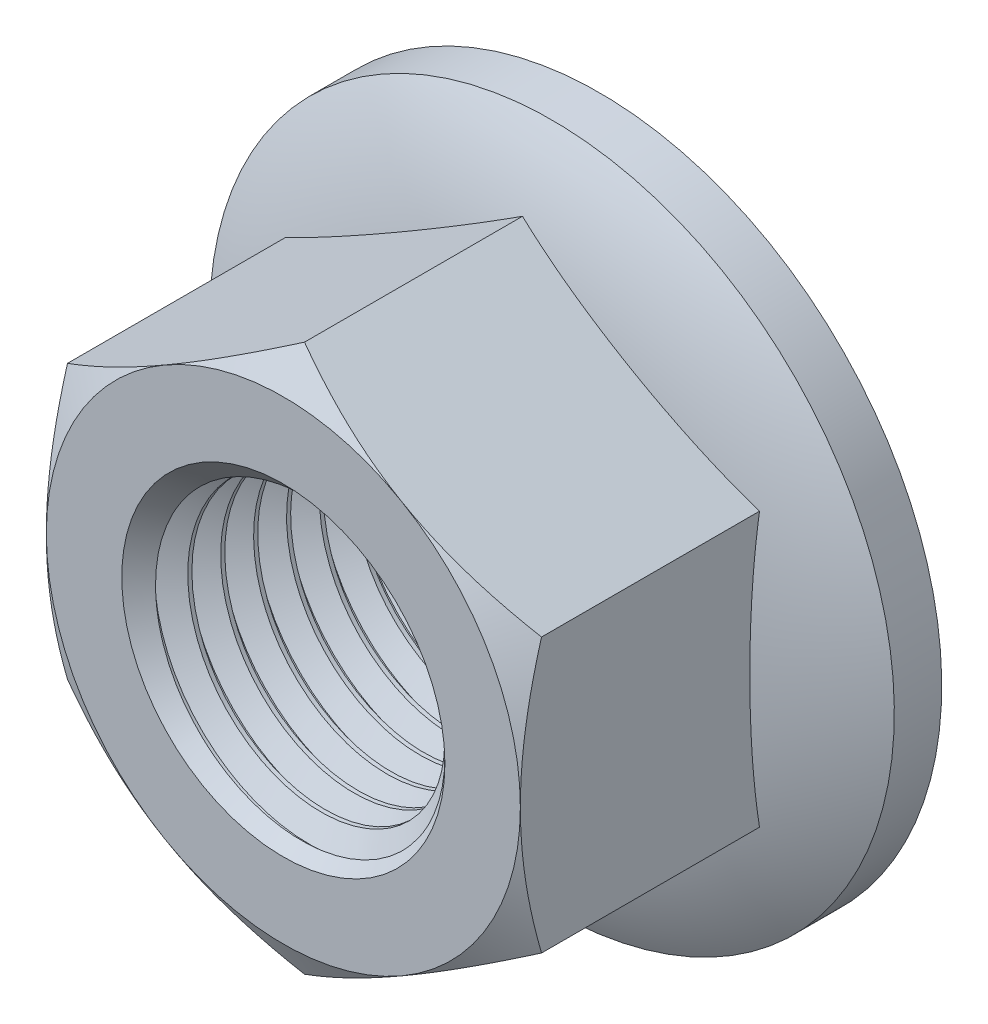
SolidWorks part; units mm, degrees
ref_plane "Front Plane" through (0, 0, 0) normal (0, 0, 1) x (1, 0, 0)
ref_plane "Top Plane" through (0, 0, 0) normal (0, 1, 0) x (1, 0, 0)
ref_plane "Right Plane" through (0, 0, 0) normal (1, 0, 0) x (0, 0, -1)
sketch "Sketch1" plane through (0, 0, 0) normal (0, 0, 1) x (1, 0, 0)
  line L1 (0, 10.3923) -> (-9, 5.1962)
  line L2 (-9, 5.1962) -> (-9, -5.1962)
  line L3 (-9, -5.1962) -> (0, -10.3923)
  line L4 (0, -10.3923) -> (9, -5.1962)
  line L5 (9, -5.1962) -> (9, 5.1962)
  line L6 (9, 5.1962) -> (0, 10.3923)
  circle A0 centre (0, 0) radius 9 construction
  dimension "Width" = 18
sketch "Sketch2" plane through (0, 0, 0) normal (1, 0, 0) x (0, 0, -1)
  line L0 (-6, 0) -> (6, 0) construction
  line L1 (6, 0) -> (6, 13)
  line L2 (6, 13) -> (4.2, 13)
  line L3 (4.2, 13) -> (4.2, 0)
  line L4 (-6, 0) -> (-6, 6)
  line L5 (-6, 6) -> (6, 6)
  line L6 (2.4, 6) -> (2.4, 13) construction
  line L7 (2.4, 13) -> (4.2, 13) construction
  arc A0 (4.2, 13) -> (2.4, 6) centre (16.9111, 6) ccw
  point P2 (0, 0)
  point P5 (-4.75, 6)
  point P12 (-6, -6)
  point P14 (-6, 6)
  dimension "Height" = 12
  dimension "Flange Diameter" = 26
  dimension "Flange Thickness" = 1.8
  dimension "Thread Diameter" = 12
  dimension "Thread Pitch" = 1.25
sketch "Sketch3" plane through (0, 0, 0) normal (0, 0, 1) x (1, 0, 0)
  line L0 (9, 5.1962) -> (0, 10.3923) construction
  line L1 (9, -5.1962) -> (9, 5.1962) construction
  line L2 (0, -10.3923) -> (9, -5.1962) construction
  line L3 (-9, -5.1962) -> (0, -10.3923) construction
  line L4 (-9, 5.1962) -> (-9, -5.1962) construction
  line L5 (0, 10.3923) -> (-9, 5.1962) construction
  line L6 (9, 5.1962) -> (0, 10.3923)
  line L7 (9, -5.1962) -> (9, 5.1962)
  line L8 (0, -10.3923) -> (9, -5.1962)
  line L9 (-9, -5.1962) -> (0, -10.3923)
  line L10 (-9, 5.1962) -> (-9, -5.1962)
  line L11 (0, 10.3923) -> (-9, 5.1962)
extrude "Boss-Extrude1" add sketch "Sketch3" against normal up to vertex (6 mm away) from vertex up to point (0, 0, -6) starting at point (0, 0, 6)
sketch "Sketch5" plane through (0, 0, 6) normal (0, 0, 1) x (1, 0, 0)
  circle A0 centre (0, 0) radius 9 construction
  circle A1 centre (0, 0) radius 9
extrude "Cut-Extrude1" cut sketch "Sketch5" against normal through all draft 60 flip side to cut
sketch "Sketch4" plane through (0, 0, 0) normal (1, 0, 0) x (0, 0, -1)
  line L0 (6, 13) -> (4.2, 13) construction
  line L1 (6, 13) -> (4.2, 13)
  line L2 (2.4, 6) -> (2.4, 0)
  line L3 (-6, 0) -> (6, 0) construction
  line L4 (2.4, 0) -> (6, 0)
  line L5 (6, 0) -> (6, 13)
  arc A0 (4.2, 13) -> (2.4, 6) centre (16.9111, 6) ccw construction
  arc A1 (4.2, 13) -> (2.4, 6) centre (16.9111, 6) ccw
revolve "Revolve1" add sketch "Sketch4" angle 360 about L4
sketch "Sketch6" plane through (0, 0, 6) normal (0, 0, 1) x (1, 0, 0)
  circle A0 centre (0, 0) radius 6
extrude "Cut-Extrude2" cut sketch "Sketch6" against normal through all
sketch "Sketch7" plane through (0, 0, 6) normal (0, 0, 1) x (1, 0, 0)
  circle A0 centre (0, 0) radius 6 construction
  circle A1 centre (0, 0) radius 6
ref_axis "Center Axis 1" through (0, 0, -6) along (0, 0, 1)
ref_plane "Contact Plane 1" through (0, 0, -6) normal (0, 0, -1) x (-1, 0, 0)
curve "Helix/Spiral1" pitch 1.25 height 13.25 radius 6 centre (0, 0, 6) axis (0, 0, -1) start towards (0, 1, 0)
sketch "Sketch8" plane through (0, 0, 0) normal (1, 0, 0) x (0, 0, -1)
  line L0 (-7.1719, 6.1353) -> (-6.5469, 5.0528) construction
  line L1 (-6.5469, 5.0528) -> (-5.9219, 6.1353) construction
  line L2 (-5.9219, 6.1353) -> (-7.1719, 6.1353) construction
  line L3 (-7.1328, 6.0677) -> (-5.9609, 6.0677)
  line L4 (-5.9609, 6.0677) -> (-6.4688, 5.1881)
  line L5 (-6.4688, 5.1881) -> (-6.625, 5.1881)
  line L6 (-6.625, 5.1881) -> (-7.1328, 6.0677)
  line L7 (-6.5469, 5.1881) -> (-6.5469, 5.0528) construction
  line L8 (-7.0938, 6) -> (-6, 6) construction
  line L9 (-6.5469, 6.1353) -> (-6.5469, 6) construction
  point P12 (-6.5469, 6.0677)
  dimension "D1" = 1.25
  dimension "D2" = 0.1562
sweep "Sweep1" add profiles "Sketch8" path "Helix/Spiral1"
sketch "Sketch9" plane through (0, 0, 6) normal (0, 0, 1) x (1, 0, 0)
  circle A0 centre (0, 0) radius 6.1353
extrude "Cut-Extrude3" cut sketch "Sketch9" against normal up to vertex (12 mm away) draft 45 and the other way through all up to point (0, 6, -6)
sketch "Sketch10" plane through (0, 0, -6) normal (0, 0, -1) x (-1, 0, 0)
  circle A1 centre (0, 0) radius 6.1353
  circle A2 centre (0, 0) radius 6.1353
  dimension "D1" = 0
extrude "Cut-Extrude4" cut sketch "Sketch10" against normal up to vertex (12 mm away) draft 45 and the other way through all up to point (0, 6, 6)
equation "\"D4@Helix/Spiral1\"=\"Thread Pitch@Sketch2\""
equation "\"D3@Helix/Spiral1\"=\"Height@Sketch2\"+\"Thread Pitch@Sketch2\""
equation "\"D2@Sketch8\"=\"D1@Sketch8\"/8"
equation "\"D1@Sketch8\"=\"Thread Pitch@Sketch2\""
